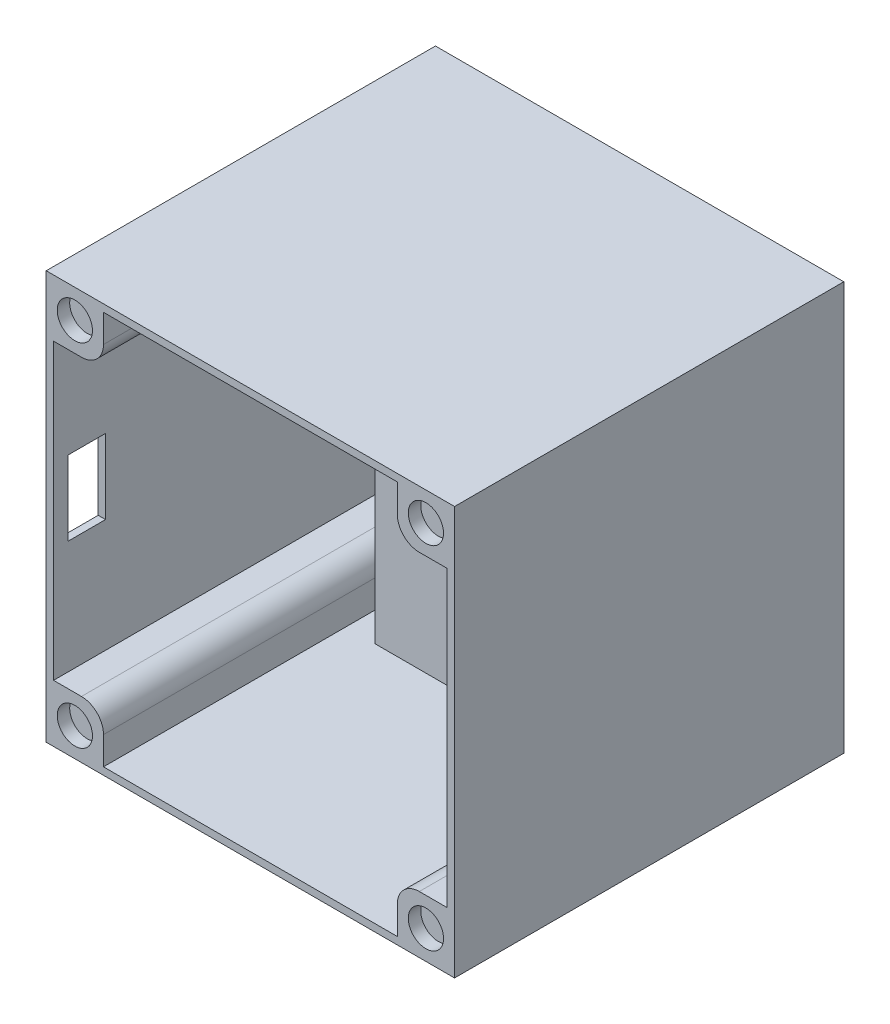
SolidWorks part; units mm, degrees
ref_plane "Přední rovina" through (0, 0, 0) normal (0, 0, 1) x (1, 0, 0)
ref_plane "Horní rovina" through (0, 0, 0) normal (0, 1, 0) x (1, 0, 0)
ref_plane "Pravá rovina" through (0, 0, 0) normal (1, 0, 0) x (0, 0, -1)
sketch "Skica1" plane through (0, 0, 0) normal (0, 0, 1) x (1, 0, 0)
  line L1 (27.8, 27.8) -> (-27.8, 27.8)
  line L2 (27.8, 27.8) -> (27.8, -27.8)
  line L3 (27.8, -27.8) -> (-27.8, -27.8)
  line L4 (-27.8, 27.8) -> (-27.8, -27.8)
  line L5 (27.8, 27.8) -> (-27.8, -27.8) construction
  line L6 (27.8, -27.8) -> (-27.8, 27.8) construction
  point P0 (0, 0)
  point P5 (-27.5, 0)
  point P11 (4.5, 0)
  dimension "D1" = 55.6
  dimension "D2" = 55.6
extrude "Přidat vysunutím2" add sketch "Skica1" along normal blind 3 contours L2 L1 L4 L3
sketch "Skica14" plane through (0, 0, 3) normal (0, 0, 1) x (1, 0, 0)
  line L1 (-27.8, 27.8) -> (27.8, 27.8)
  line L2 (-27.8, 27.8) -> (-27.8, -27.8)
  line L3 (-27.8, -27.8) -> (27.8, -27.8)
  line L4 (27.8, 27.8) -> (27.8, -27.8)
  line L5 (-26.8, 26.8) -> (26.8, 26.8)
  line L6 (-26.8, 26.8) -> (-26.8, -27.8)
  line L7 (-26.8, -27.8) -> (26.8, -27.8)
  line L8 (26.8, 26.8) -> (26.8, -27.8)
  line L9 (-26.8, -27.8) -> (26.8, -27.8)
  line L10 (-26.8, -27.8) -> (-26.8, -26.8)
  line L11 (-26.8, -26.8) -> (26.8, -26.8)
  line L12 (26.8, -27.8) -> (26.8, -26.8)
  line M13 (-27.8, -27.8) -> (27.8, -27.8)
  line M14 (27.8, -27.8) -> (27.8, 27.8)
  line M15 (27.8, 27.8) -> (-27.8, 27.8)
  line M16 (-27.8, 27.8) -> (-27.8, -27.8)
  dimension "D1" = 1
  dimension "D2" = 1
  dimension "D3" = 1
  dimension "D4" = 0
  dimension "D5" = 1
  dimension "D6" = 53.6
extrude "Přidat vysunutím9" add sketch "Skica14" along normal blind 50 contours L5 L8 L6 M13 M14 M15 M16 | L10 L9 L12 L11 region at (0, 27.0137, 3)
sketch "Skica19" plane through (0, 0, 0) normal (0, 0, -1) x (-1, 0, 0)
  line L1 (-27.8, 27.8) -> (-20, 27.8)
  line L2 (-27.8, 27.8) -> (-27.8, 20)
  line L3 (-27.8, 20) -> (-20, 20)
  line L4 (-20, 27.8) -> (-20, 20)
  line L5 (27.8, 27.8) -> (20, 27.8)
  line L6 (27.8, 27.8) -> (27.8, 20)
  line L7 (27.8, 20) -> (20, 20)
  line L8 (20, 27.8) -> (20, 20)
  line L9 (-27.8, -27.8) -> (-20, -27.8)
  line L10 (-27.8, -27.8) -> (-27.8, -20)
  line L11 (-27.8, -20) -> (-20, -20)
  line L12 (-20, -27.8) -> (-20, -20)
  line L13 (27.8, -27.8) -> (20, -27.8)
  line L14 (27.8, -27.8) -> (27.8, -20)
  line L15 (27.8, -20) -> (20, -20)
  line L16 (20, -27.8) -> (20, -20)
  dimension "D1" = 7.8
  dimension "D2" = 7.8
  dimension "D3" = 7.8
  dimension "D4" = 7.8
extrude "Přidat vysunutím10" add sketch "Skica19" against normal blind 53
sketch "Skica20" plane through (0, 0, 53) normal (0, 0, 1) x (1, 0, 0)
  line L0 (-27.8, -27.8) -> (27.8, -27.8) construction
  line L1 (-20, -26.8) -> (-20, -20) construction
  line L2 (-27.8, 27.8) -> (-27.8, -27.8) construction
  line L3 (27.8, 27.8) -> (-27.8, 27.8) construction
  line L4 (27.8, -27.8) -> (27.8, 27.8) construction
  line L5 (-27.8, -27.8) -> (27.8, -27.8) construction
  circle A0 centre (-23.9, -23.9) radius 2.4
  circle A1 centre (-23.9, 23.9) radius 2.4
  circle A2 centre (23.9003, 23.9) radius 2.4
  circle A3 centre (23.9003, -23.9) radius 2.4
  dimension "D1" = 4.8
  dimension "D4" = 4.8
  dimension "D5" = 3.9
  dimension "D7" = 4.8
  dimension "D10" = 4.8
  dimension "D2" = 3.9
  dimension "D3" = 3.9
  dimension "D6" = 3.9
  dimension "D8" = 3.8997
  dimension "D9" = 3.9
  dimension "D11" = 3.9
  dimension "D12" = 3.8997
extrude "Odebrat vysunutím9" cut sketch "Skica20" against normal blind 1.7
fillet "Zaoblit1" radius 3 4 edges at (20, 20, 28) (20, -20, 28) (-20, -20, 28) (-20, 20, 28)
sketch "Skica25" plane through (0, 0, 0) normal (0, 0, -1) x (-1, 0, 0)
  line L0 (27.8, 27.8) -> (27.8, -27.8) construction
  line L1 (16, 27.8) -> (-16, 27.8)
  line L2 (16, 27.8) -> (16, -27.8)
  line L3 (16, -27.8) -> (-16, -27.8)
  line L4 (-16, 27.8) -> (-16, -27.8)
  line L5 (-27.8, 27.8) -> (27.8, 27.8) construction
  dimension "D1" = 55.6
  dimension "D2" = 32
  dimension "D3" = 11.8
  dimension "D4" = 0
extrude "Přidat vysunutím12" add sketch "Skica25" against normal blind 20
sketch "Skica26" plane through (0, 0, 0) normal (0, 0, -1) x (-1, 0, 0)
  line L0 (-27.8, 27.8) -> (-27.8, -27.8) construction
  line L1 (-15, 26.5) -> (15, 26.5)
  line L2 (-15, 26.5) -> (-15, -26.5)
  line L3 (-15, -26.5) -> (15, -26.5)
  line L4 (15, 26.5) -> (15, -26.5)
  line L5 (-27.8, 27.8) -> (27.8, 27.8) construction
  line L6 (-27.8, -27.8) -> (27.8, -27.8) construction
  dimension "D1" = 53
  dimension "D2" = 30
  dimension "D3" = 12.8
  dimension "D4" = 1.3
  dimension "D5" = 1.3
  dimension "D6" = 1.3
extrude "Odebrat vysunutím11" cut sketch "Skica26" against normal blind 19
sketch "Skica27" plane through (-27.8, 0, 0) normal (-1, 0, 0) x (0, 0, 1)
  line L0 (53, 27.8) -> (0, 27.8) construction
  line L1 (51, 5.58) -> (45.92, 5.58)
  line L2 (51, 5.58) -> (51, -4.58)
  line L3 (51, -4.58) -> (45.92, -4.58)
  line L4 (45.92, 5.58) -> (45.92, -4.58)
  line L5 (53, -27.8) -> (0, -27.8) construction
  line L6 (53, 27.8) -> (53, -27.8) construction
  dimension "D1" = 10.16
  dimension "D2" = 5.08
  dimension "D3" = 22.22
  dimension "D4" = 23.22
  dimension "D5" = 2
extrude "Odebrat vysunutím12" cut sketch "Skica27" against normal blind 1
sketch "Skica28" plane through (0, 0, 0) normal (0, 0, -1) x (-1, 0, 0)
  line L0 (-15, 26.5) -> (-15, -26.5) construction
  line L1 (-15, 20.9403) -> (-24, 20.9403)
  line L2 (-15, 20.9403) -> (-15, 12.9403)
  line L3 (-15, 12.9403) -> (-24, 12.9403)
  line L4 (-24, 20.9403) -> (-24, 12.9403)
  dimension "D1" = 8
  dimension "D2" = 9
extrude "Odebrat vysunutím13" cut sketch "Skica28" against normal blind 1
fillet "Zaoblit3" radius 4 2 edges at (24, 12.9403, 0.5) (24, 20.9403, 0.5)
sketch "Skica29" plane through (-15, 0, 0) normal (1, 0, 0) x (0, 0, -1)
  line L0 (0, -26.5) -> (0, 26.5) construction
  line L1 (-1, 21.5) -> (-0.5, 21.5)
  line L2 (-1, 21.5) -> (-1, 17.5)
  line L3 (-1, 17.5) -> (-0.5, 17.5)
  line L4 (-0.5, 21.5) -> (-0.5, 17.5)
  line L5 (-19, -26.5) -> (0, -26.5) construction
  line L6 (-1.08, -17.5) -> (-0.58, -17.5)
  line L7 (-1.08, -17.5) -> (-1.08, -21.5)
  line L8 (-1.08, -21.5) -> (-0.58, -21.5)
  line L9 (-0.58, -17.5) -> (-0.58, -21.5)
  line L10 (-19, 26.5) -> (0, 26.5) construction
  dimension "D1" = 4
  dimension "D2" = 0.5
  dimension "D3" = 0.5
  dimension "D4" = 4
  dimension "D5" = 0.5
  dimension "D6" = 0.58
  dimension "D7" = 5
  dimension "D8" = 5
extrude "Odebrat vysunutím14" cut sketch "Skica29" against normal blind 2
sketch "Skica30" plane through (0, 0, 1) normal (0, 0, -1) x (-1, 0, 0)
  circle A0 centre (-20, 16.9403) radius 0.9
  dimension "D1" = 1.8
  dimension "D2" = 4
  dimension "D3" = 4
extrude "Odebrat vysunutím15" cut sketch "Skica30" against normal blind 2
sketch "Skica31" plane through (0, 0, 19) normal (0, 0, -1) x (-1, 0, 0)
  line L1 (-15, 26.5) -> (-9, 26.5)
  line L2 (-15, 26.5) -> (-15, 22.5)
  line L3 (-15, 22.5) -> (-9, 22.5)
  line L4 (-9, 26.5) -> (-9, 22.5)
  dimension "D1" = 4
  dimension "D2" = 6
extrude "Odebrat vysunutím16" cut sketch "Skica31" against normal blind 2
fillet "Zaoblit4" radius 1 1 edges at (9, 22.5, 19.5)
